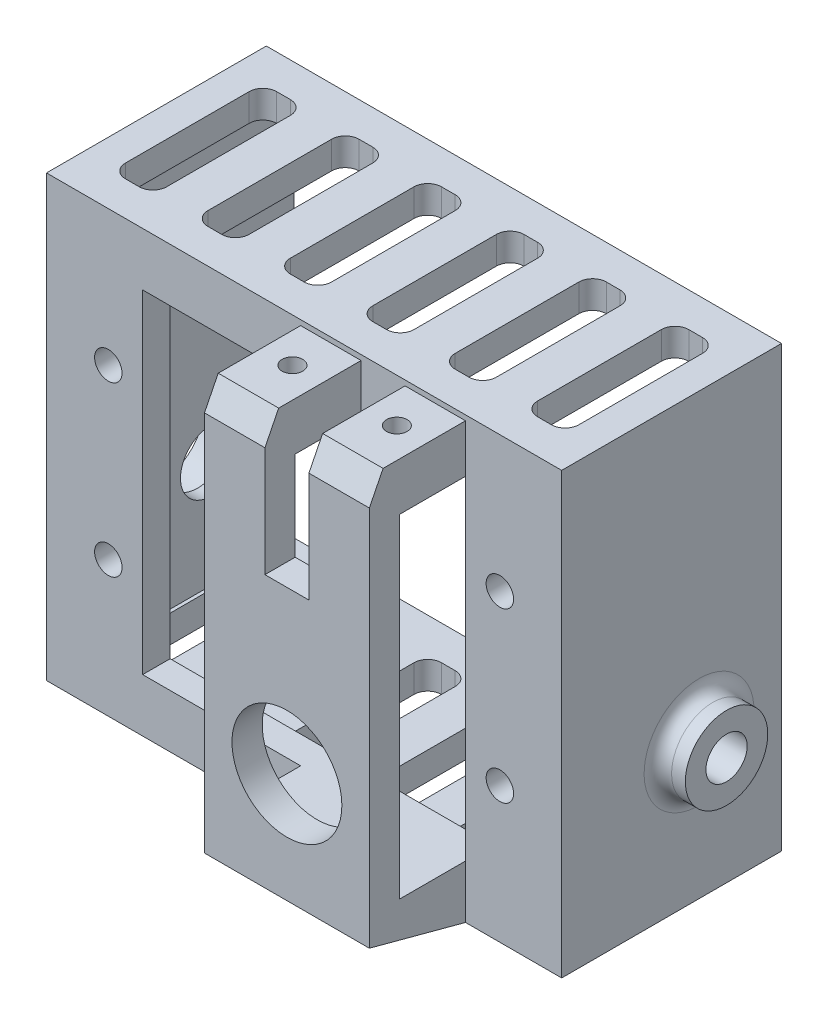
SolidWorks part; units mm, degrees
ref_plane "前视基准面" through (0, 0, 0) normal (0, 0, 1) x (1, 0, 0)
ref_plane "上视基准面" through (0, 0, 0) normal (0, 1, 0) x (1, 0, 0)
ref_plane "右视基准面" through (0, 0, 0) normal (1, 0, 0) x (0, 0, -1)
sketch "草图1" plane through (0, 0, 0) normal (0, 0, 1) x (1, 0, 0)
  line L0 (0, 16.832) -> (0, -37.7985) construction
  line L1 (-34.0238, 0) -> (58.9478, 0) construction
  line L2 (-20, 0) -> (-20, 8.7719) construction
  line L3 (8.5, 0) -> (8.5, 10.2817) construction
  line L4 (-20, 6) -> (8.5, 6) construction
  line L5 (-5.75, 8.9788) -> (-5.75, 6) construction
  line L6 (-17.5, 6) -> (-17.5, -18.25)
  line L7 (6, 6) -> (6, -18.25)
  line L8 (10.25, 6) -> (6, 6) construction
  line L9 (-17.5, 6) -> (6, 6)
  line L10 (-17.5, -18.25) -> (6, -18.25)
  line L11 (-22.5, 9.875) -> (11, 9.875)
  line L12 (11, 9.875) -> (11, -22.125)
  line L13 (-22.5, 9.875) -> (-22.5, -22.125)
  line L14 (-22.5, -22.125) -> (11, -22.125)
  line L15 (-17.5, -6.125) -> (6, -6.125) construction
  circle A0 centre (-20, 0) radius 1
  circle A1 centre (8.5, 0) radius 1
  circle A2 centre (-20, -12.25) radius 1
  circle A3 centre (8.5, -12.25) radius 1
  dimension "D3" = 2
  dimension "D1" = 23.5
  dimension "D2" = 24.25
  dimension "D4" = 16
  dimension "D5" = 16
  dimension "D6" = 5
  dimension "D7" = 5
extrude "凸台-拉伸1" add sketch "草图1" along normal blind 2
ref_plane "基准面4" through (0, 0, 9) normal (0, 0, 1) x (1, 0, 0)
sketch "草图2" plane through (0, 0, 9) normal (0, 0, 1) x (1, 0, 0)
  line L0 (-17.5, -6.125) -> (6, -6.125) construction
  line L1 (-17.5, 6) -> (-17.5, -18.25) construction
  line L2 (6, -18.25) -> (6, 6) construction
  line L3 (-5.75, 6) -> (-5.75, -18.25) construction
  line L4 (6, 6) -> (-17.5, 6) construction
  line L5 (-17.5, -18.25) -> (6, -18.25) construction
  line L6 (-20, -12.25) -> (8.5, -12.25) construction
  line L7 (-20, 0) -> (8.5, 0) construction
  line L9 (6, -6.25) -> (-6, -6.25)
  line L10 (6, -6.25) -> (6, -18.25)
  line L11 (6, -18.25) -> (-6, -18.25)
  line L12 (-6, -6.25) -> (-6, -18.25)
  line L13 (6, -6.25) -> (-6, -18.25) construction
  line L14 (6, -18.25) -> (-6, -6.25) construction
  circle A0 centre (0, -12.25) radius 6 construction
  circle A2 centre (0, -12.25) radius 4
  dimension "D2" = 12
  dimension "D3" = 8
  dimension "D1" = 8.5
  dimension "D4" = 12
extrude "凸台-拉伸2" add sketch "草图2" against normal blind 2.2 separate body
sketch "草图3" plane through (-6, 0, 0) normal (-1, 0, 0) x (0, 0, 1)
  line L0 (9, -18.25) -> (2, -18.25)
  line L1 (2, -18.25) -> (2, -22.125)
  line L2 (2, 9.875) -> (2, -22.125) construction
  line L3 (2, -22.125) -> (0, -22.125) construction
  line L4 (2, -22.125) -> (9, -20.25)
  line L5 (9, -20.25) -> (9, -18.25)
  dimension "D1" = 2
extrude "凸台-拉伸3" add sketch "草图3" against normal up to surface (12 mm away) up to face at (6, -12.25, 7.9)
sketch "草图4" plane through (-6, 0, 0) normal (-1, 0, 0) x (0, 0, 1)
  line L0 (6.8, -6.25) -> (9, -6.25)
  line L1 (9, -6.25) -> (9, 9.5)
  line L2 (9, 9.5) -> (2, 9.5)
  line L3 (6.8, -6.25) -> (6.8, 6)
  line L4 (6.8, 6) -> (2, 6)
  line L5 (2, 6) -> (2, 9.5)
  dimension "D1" = 3.5
extrude "凸台-拉伸4" add sketch "草图4" against normal up to surface (12 mm away) up to face at (6, -15.2292, 5.9333)
sketch "草图5" plane through (0, 0, 0) normal (0, 0, -1) x (-1, 0, 0)
  line L0 (-11, 9.875) -> (22.5, 9.875)
  line L1 (22.5, 9.875) -> (22.5, 7.875)
  line L2 (22.5, 9.875) -> (22.5, -22.125) construction
  line L3 (22.5, 7.875) -> (-11, 7.875)
  line L4 (-11, -22.125) -> (-11, 9.875) construction
  line L5 (-11, 7.875) -> (-11, 9.875)
  line L6 (-6, -6.125) -> (17.5, -6.125) construction
  line L7 (-6, -18.25) -> (-6, 6) construction
  line L8 (17.5, 6) -> (17.5, -18.25) construction
  line L9 (-11, -20.125) -> (-11, -22.125)
  line L10 (22.5, -20.125) -> (-11, -20.125)
  line L11 (22.5, -22.125) -> (22.5, -20.125)
  line L12 (-11, -22.125) -> (22.5, -22.125)
  dimension "D1" = 2
extrude "凸台-拉伸5" add sketch "草图5" along normal blind 14
sketch "草图7" plane through (0, 0, 2) normal (0, 0, 1) x (1, 0, 0)
  line L0 (-5.75, 9.875) -> (-5.75, 15.8183) construction
  line L1 (11, 9.875) -> (-22.5, 9.875) construction
  line L2 (-22.5, 9.875) -> (-24.5, 9.875)
  line L3 (-24.5, -22.125) -> (-22.5, -22.125)
  line L4 (-22.5, -22.125) -> (-22.5, 9.875)
  line L5 (-24.5, 9.875) -> (-24.5, -22.125)
  line L6 (13, 9.875) -> (13, -22.125)
  line L7 (11, -22.125) -> (11, 9.875)
  line L8 (13, -22.125) -> (11, -22.125)
  line L9 (11, 9.875) -> (13, 9.875)
  dimension "D1" = 2
extrude "凸台-拉伸6" add sketch "草图7" against normal blind 16
ref_plane "基准面5" through (0, 0, -8) normal (0, 0, -1) x (-1, 0, 0)
sketch "草图8" plane through (0, 0, -8) normal (0, 0, -1) x (-1, 0, 0)
  line L0 (-6, -6.125) -> (2.8741, -6.125) construction
  line L1 (-6, -18.25) -> (-6, 6) construction
  line L2 (20, -12.25) -> (-19.2584, -12.25) construction
  line L3 (20, -12.25) -> (28.1936, -12.25) construction
sketch "草图9" plane through (-24.5, 0, 0) normal (1, 0, 0) x (0, 0, -1)
  line L0 (8, -17.6) -> (8, 17.6) construction
  circle A0 centre (8, -12.25) radius 3.625
  dimension "D1" = 7.25
extrude "切除-拉伸1" cut sketch "草图9" along normal blind 1
sketch "草图10" plane through (-23.5, 0, 0) normal (-1, 0, 0) x (0, 0, 1)
  circle A0 centre (-8, -12.25) radius 2.25
  dimension "D1" = 4.5
extrude "切除-拉伸2" cut sketch "草图10" against normal blind 1
sketch "草图11" plane through (-24.5, 0, 0) normal (1, 0, 0) x (0, 0, -1)
  circle A0 centre (8, -12.25) radius 5
  circle A1 centre (8, -12.25) radius 3.625 construction
  circle A2 centre (8, -12.25) radius 3.625
  dimension "D1" = 10
extrude "凸台-拉伸7" add sketch "草图11" against normal blind 2
fillet "圆角1" radius 1 1 edges at (-24.5, -17.25, -8)
sketch "草图12" plane through (13, 0, 0) normal (-1, 0, 0) x (0, 0, 1)
  circle A0 centre (-8, -12.25) radius 1.5
  circle A1 centre (-8, -12.25) radius 3
  dimension "D1" = 3
  dimension "D2" = 6
extrude "凸台-拉伸8" add sketch "草图12" against normal blind 2
fillet "圆角2" radius 1 1 edges at (13, -9.25, -8)
sketch "草图13" plane through (13, 0, 0) normal (-1, 0, 0) x (0, 0, 1)
  circle A0 centre (-8, -12.25) radius 1.5 construction
  circle A1 centre (-8, -12.25) radius 1.5
extrude "切除-拉伸3" cut sketch "草图13" along normal blind 2
sketch "草图14" [suppressed] plane through (13, 0, 0) normal (1, 0, 0) x (0, 0, -1)
  circle A0 centre (8, -12.25) radius 3.625
  dimension "D1" = 7.25
extrude "切除-拉伸4" [suppressed] cut sketch "草图14" against normal blind 1
sketch "草图15" [suppressed] plane through (12, 0, 0) normal (1, 0, 0) x (0, 0, -1)
  circle A0 centre (8, -12.25) radius 2.25
  dimension "D1" = 4.5
extrude "切除-拉伸5" [suppressed] cut sketch "草图15" against normal blind 1
sketch "草图16" [suppressed] plane through (13, 0, 0) normal (1, 0, 0) x (0, 0, -1)
  circle A0 centre (8, -12.25) radius 5
  circle A1 centre (8, -12.25) radius 3.625 construction
  circle A2 centre (8, -12.25) radius 3.625
  dimension "D1" = 10
extrude "凸台-拉伸9" [suppressed] add sketch "草图16" along normal blind 2
fillet "圆角3" [suppressed] radius 1
sketch "草图17" [suppressed] plane through (-24.5, 0, 0) normal (-1, 0, 0) x (0, 0, 1)
  circle A0 centre (-8, -12.25) radius 1.5
  circle A1 centre (-8, -12.25) radius 3
  dimension "D1" = 3
  dimension "D2" = 6
extrude "凸台-拉伸10" [suppressed] add sketch "草图17" along normal blind 2
fillet "圆角4" [suppressed] radius 1
sketch "草图18" [suppressed] plane through (-24.5, 0, 0) normal (-1, 0, 0) x (0, 0, 1)
  circle A3 centre (-8, -12.25) radius 1.5
  circle A4 centre (-8, -12.25) radius 1.5
  dimension "D1" = 0
extrude "切除-拉伸6" [suppressed] cut sketch "草图18" against normal blind 2
sketch "草图19" plane through (0, 9.5, 0) normal (0, 1, 0) x (1, 0, 0)
  line L0 (0, -9) -> (0, -2) construction
  line L1 (6, -9) -> (-6, -9) construction
  line L2 (13, -2) -> (-24.5, -2) construction
  line L3 (-1.6005, -2) -> (1.6005, -2)
  line L4 (6, -2) -> (-6, -2) construction
  line L5 (1.6005, -2) -> (1.6005, -9)
  line L6 (1.6005, -9) -> (-1.6005, -9)
  line L7 (-1.6005, -2) -> (-1.6005, -9)
  dimension "D1" = 3.201
extrude "切除-拉伸7" cut sketch "草图19" against normal blind 10
sketch "草图20" plane through (0, 9.875, 0) normal (0, 1, 0) x (1, 0, 0)
  line L0 (-5.75, 14) -> (-5.75, -2) construction
  line L1 (-24.5, 14) -> (13, 14) construction
  line L2 (13, -2) -> (-24.5, -2) construction
  line L3 (-7.25, 10.5) -> (-7.25, 1.5)
  line L4 (-8.25, 0.5) -> (-9.25, 0.5)
  line L5 (-10.25, 1.5) -> (-10.25, 10.5)
  line L6 (-9.25, 11.5) -> (-8.25, 11.5)
  line L7 (7.75, 10.5) -> (7.75, 1.5)
  line L8 (-15.25, 11.5) -> (-14.25, 11.5)
  line L9 (-16.25, 10.5) -> (-16.25, 1.5)
  line L10 (-15.25, 0.5) -> (-14.25, 0.5)
  line L11 (-13.25, 10.5) -> (-13.25, 1.5)
  line L12 (-21.25, 11.5) -> (-20.25, 11.5)
  line L13 (-22.25, 10.5) -> (-22.25, 1.5)
  line L14 (-21.25, 0.5) -> (-20.25, 0.5)
  line L15 (-19.25, 10.5) -> (-19.25, 1.5)
  line L16 (9.75, 0.5) -> (8.75, 0.5)
  line L17 (10.75, 10.5) -> (10.75, 1.5)
  line L18 (9.75, 11.5) -> (8.75, 11.5)
  line L19 (1.75, 10.5) -> (1.75, 1.5)
  line L20 (3.75, 0.5) -> (2.75, 0.5)
  line L21 (4.75, 10.5) -> (4.75, 1.5)
  line L22 (3.75, 11.5) -> (2.75, 11.5)
  line L23 (-2.25, 11.5) -> (-3.25, 11.5)
  line L24 (-1.25, 1.5) -> (-1.25, 10.5)
  line L25 (-3.25, 0.5) -> (-2.25, 0.5)
  line L26 (-4.25, 10.5) -> (-4.25, 1.5)
  arc A0 (3.75, 0.5) -> (4.75, 1.5) centre (3.75, 1.5) ccw
  arc A1 (1.75, 1.5) -> (2.75, 0.5) centre (2.75, 1.5) ccw
  arc A2 (-1.25, 1.5) -> (-2.25, 0.5) centre (-2.25, 1.5) cw
  arc A3 (-3.25, 0.5) -> (-4.25, 1.5) centre (-3.25, 1.5) cw
  arc A4 (-7.25, 1.5) -> (-8.25, 0.5) centre (-8.25, 1.5) cw
  arc A5 (-9.25, 0.5) -> (-10.25, 1.5) centre (-9.25, 1.5) cw
  arc A6 (-14.25, 0.5) -> (-13.25, 1.5) centre (-14.25, 1.5) ccw
  arc A7 (-16.25, 1.5) -> (-15.25, 0.5) centre (-15.25, 1.5) ccw
  arc A8 (-20.25, 0.5) -> (-19.25, 1.5) centre (-20.25, 1.5) ccw
  arc A9 (-22.25, 1.5) -> (-21.25, 0.5) centre (-21.25, 1.5) ccw
  arc A10 (7.75, 1.5) -> (8.75, 0.5) centre (8.75, 1.5) ccw
  arc A11 (9.75, 0.5) -> (10.75, 1.5) centre (9.75, 1.5) ccw
  arc A12 (7.75, 10.5) -> (8.75, 11.5) centre (8.75, 10.5) cw
  arc A13 (10.75, 10.5) -> (9.75, 11.5) centre (9.75, 10.5) ccw
  arc A14 (4.75, 10.5) -> (3.75, 11.5) centre (3.75, 10.5) ccw
  arc A15 (1.75, 10.5) -> (2.75, 11.5) centre (2.75, 10.5) cw
  arc A16 (-2.25, 11.5) -> (-1.25, 10.5) centre (-2.25, 10.5) cw
  arc A17 (-3.25, 11.5) -> (-4.25, 10.5) centre (-3.25, 10.5) ccw
  arc A18 (-7.25, 10.5) -> (-8.25, 11.5) centre (-8.25, 10.5) ccw
  arc A19 (-10.25, 10.5) -> (-9.25, 11.5) centre (-9.25, 10.5) cw
  arc A20 (-14.25, 11.5) -> (-13.25, 10.5) centre (-14.25, 10.5) cw
  arc A21 (-15.25, 11.5) -> (-16.25, 10.5) centre (-15.25, 10.5) ccw
  arc A22 (-20.25, 11.5) -> (-19.25, 10.5) centre (-20.25, 10.5) cw
  arc A23 (-21.25, 11.5) -> (-22.25, 10.5) centre (-21.25, 10.5) ccw
  point P30 (9.25, 0.5)
  point P33 (4.75, 0.5)
  point P36 (1.75, 0.5)
  point P39 (-1.25, 0.5)
  point P42 (-4.25, 0.5)
  point P45 (-7.25, 0.5)
  point P48 (-10.25, 0.5)
  point P51 (-13.25, 0.5)
  point P54 (-16.25, 0.5)
  point P57 (-19.25, 0.5)
  point P60 (-22.25, 0.5)
  point P63 (7.75, 0.5)
  point P66 (10.75, 0.5)
  point P69 (7.75, 11.5)
  point P72 (10.75, 11.5)
  point P75 (4.75, 11.5)
  point P78 (1.75, 11.5)
  point P81 (-1.25, 11.5)
  point P84 (-4.25, 11.5)
  point P87 (-7.25, 11.5)
  point P90 (-10.25, 11.5)
  point P93 (-13.25, 11.5)
  point P96 (-16.25, 11.5)
  point P99 (-19.25, 11.5)
  point P102 (-22.25, 11.5)
  dimension "D9" = 1
  dimension "D1" = 3
  dimension "D2" = 3
  dimension "D3" = 3
  dimension "D4" = 3
  dimension "D5" = 3
  dimension "D6" = 3
  dimension "D7" = 2.5
  dimension "D8" = 2.5
extrude "切除-拉伸8" cut sketch "草图20" against normal blind 42
sketch "草图22" plane through (0, 9.5, 0) normal (0, 1, 0) x (1, 0, 0)
  line L0 (0, -2) -> (0, -9) construction
  line L1 (13, -2) -> (-24.5, -2) construction
  line L2 (-1.6005, -9) -> (1.6005, -9) construction
  line L3 (6, -2) -> (1.6005, -2) construction
  circle A0 centre (3.8, -4.8) radius 0.75
  circle A1 centre (-3.8, -4.8) radius 0.75
  dimension "D2" = 2.8
  dimension "D3" = 1.5
  dimension "D1" = 3.8
extrude "切除-拉伸9" cut sketch "草图22" against normal blind 5
chamfer "倒角1" distance 1 distance2 2 2 edges at (3.8002, 9.5, 9) (-3.8002, 9.5, 9) first distance on face at (3.8, 9.5, 5.55) first distance on face at (-3.8, 9.5, 4.05)
